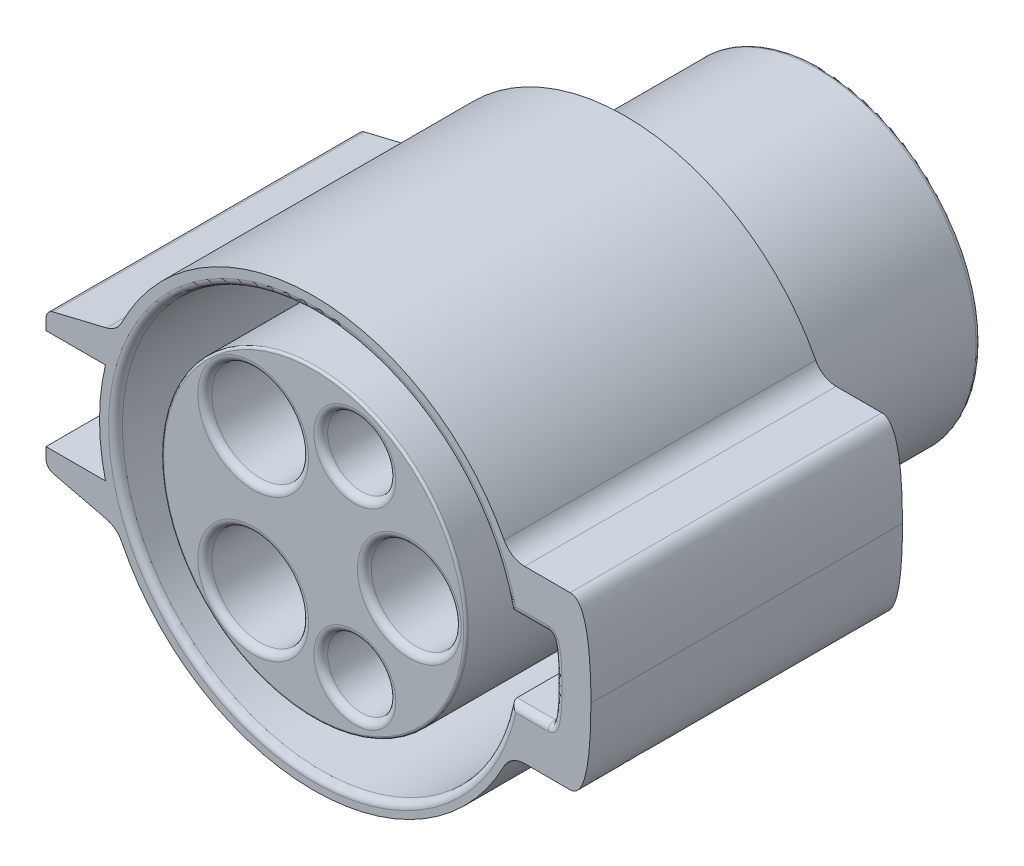
SolidWorks part; units mm, degrees
ref_plane "Front Plane" through (0, 0, 0) normal (0, 0, 1) x (1, 0, 0)
ref_plane "Top Plane" through (0, 0, 0) normal (0, 1, 0) x (1, 0, 0)
ref_plane "Right Plane" through (0, 0, 0) normal (1, 0, 0) x (0, 0, -1)
sketch "Sketch1" plane through (0, 0, 0) normal (0, 0, 1) x (-1, 0, 0)
  line L0 (21.5636, -9.4046) -> (28.6554, -7.6949)
  line L1 (29.4084, -6.7135) -> (29.4084, -5.5277)
  line L2 (29.4084, -5.5277) -> (22.8364, -5.5277)
  line L3 (22.8364, 5.5213) -> (29.4084, 5.5213)
  line L4 (-28.2678, -9.3983) -> (-21.6527, -9.3983)
  line L5 (-21.6499, 9.3983) -> (-28.2678, 9.3983)
  line L6 (29.4084, 5.5213) -> (29.4084, 6.702)
  line L7 (28.6554, 7.6834) -> (21.5636, 9.3983)
  line L14 (-25.8569, -4.2807) -> (-21.6527, -4.2807)
  line L17 (-21.6805, 4.2804) -> (-25.8569, 4.2804)
  circle A1 centre (-0.0432, -0.0032) radius 16.764
  arc A5 (-21.6805, 4.2804) -> (-21.6527, -4.2807) centre (-0.1647, 0.0697) cw
  arc A6 (28.6554, -7.6949) -> (29.4084, -6.7135) centre (28.3924, -6.7135) ccw
  arc A14 (29.4084, 6.702) -> (28.6554, 7.6834) centre (28.3924, 6.702) ccw
  arc A17 (-21.6499, 9.3983) -> (21.5636, 9.3983) centre (-0.0432, -0.0032) cw
  arc A18 (22.8636, 5.5213) -> (22.8636, -5.5277) centre (-0.0432, -0.0032) cw
  arc A19 (21.5636, -9.4046) -> (-21.6527, -9.3983) centre (-0.0432, -0.0032) cw
  spline S4 degree 3 poles (-28.2678, 9.3983) (-28.4851, 9.4005) (-28.824, 9.2766) (-29.1971, 8.9393) (-29.4861, 8.4857) (-29.7884, 7.7976) (-30.0551, 6.8265) (-30.2703, 5.5562) (-30.4123, 4.2127) (-30.5275, 2.3814) (-30.5538, 0.9563) (-30.5538, 0) knots 0.008178 0.008178 0.008178 0.008178 0.0625 0.125 0.1875 0.25 0.375 0.5 0.625 0.75 0.991406 0.991406 0.991406 0.991406 weights 1 1 1 1 1 1 1 1 1 1 1 1
  spline S5 degree 3 poles (-30.5538, 0) (-30.5538, -0.9571) (-30.5275, -2.3834) (-30.412, -4.2161) (-30.2697, -5.5604) (-30.0541, -6.8314) (-29.7867, -7.8028) (-29.4835, -8.4907) (-29.1934, -8.9439) (-28.8202, -9.2785) (-28.4823, -9.4007) (-28.2678, -9.3983) knots 0.008575 0.008575 0.008575 0.008575 0.25 0.375 0.5 0.625 0.75 0.8125 0.875 0.9375 0.991042 0.991042 0.991042 0.991042 weights 1 1 1 1 1 1 1 1 1 1 1 1
  spline S10 degree 3 poles (-25.8569, 4.2804) (-25.8911, 4.2808) (-25.9613, 4.2635) (-26.0812, 4.1882) (-26.1906, 4.0282) (-26.2866, 3.801) (-26.3835, 3.4669) (-26.4672, 3.0119) (-26.5335, 2.4318) (-26.5768, 1.8286) (-26.6112, 1.0239) (-26.619, 0.4081) (-26.6189, 0) knots 0.011727 0.011727 0.011727 0.011727 0.03125 0.0625 0.125 0.1875 0.25 0.375 0.5 0.625 0.75 0.986732 0.986732 0.986732 0.986732 weights 1 1 1 1 1 1 1 1 1 1 1 1 1
  spline S11 degree 3 poles (-26.6189, 0) (-26.619, -0.4097) (-26.6111, -1.0278) (-26.5764, -1.8353) (-26.5327, -2.4403) (-26.4657, -3.0221) (-26.381, -3.478) (-26.2827, -3.8122) (-26.1847, -4.0386) (-26.0733, -4.1975) (-25.9519, -4.266) (-25.8849, -4.2809) (-25.8569, -4.2807) knots 0.013201 0.013201 0.013201 0.013201 0.25 0.375 0.5 0.625 0.75 0.8125 0.875 0.9375 0.96875 0.984802 0.984802 0.984802 0.984802 weights 1 1 1 1 1 1 1 1 1 1 1 1 1
  point P2 (21.5636, -9.4046)
  point P5 (21.5636, 9.3983)
  point P7 (0, 0)
  point P10 (-21.5632, -9.461)
  point P11 (-21.6527, -9.3983)
extrude "Boss-Extrude2" add sketch "Sketch1" along normal blind 31.75 contours S4 S5 L4 A19 L0 A6 L1 L2 A18 L3 L6 A14 L7 A17 L5 S11 S10 L17 A5 L14 | A1 region at (0.0465, 22.804, 0) region at (0.0432, 0.0032, 0)
sketch "sockets" plane through (0, 0, 31.75) normal (0, 0, 1) x (1, 0, 0)
  circle A0 centre (10.5791, 0) radius 4.953
  circle A1 centre (4.572, -10.541) radius 3.7465
  circle A2 centre (-6.604, -7.8359) radius 5.334
  circle A3 centre (-6.604, 7.8359) radius 5.334
  circle A4 centre (4.572, 10.541) radius 3.7465
sketch "Sketch3" plane through (0, 0, 0) normal (0, 0, 1) x (1, 0, 0)
  line L8 (-29.4084, 5.5277) -> (-22.8636, 5.5277)
  line L9 (-29.4084, 6.7135) -> (-29.4084, 5.5277)
  line L10 (-21.5636, 9.4046) -> (-28.6554, 7.6949)
  line L11 (28.2678, 9.3983) -> (21.6527, 9.3983)
  line L12 (21.6499, -9.3983) -> (28.2678, -9.3983)
  line L13 (-28.6554, -7.6834) -> (-21.5636, -9.3983)
  line L14 (-29.4084, -5.5213) -> (-29.4084, -6.702)
  line L15 (-22.8636, -5.5213) -> (-29.4084, -5.5213)
  line L16 (-29.4084, 5.5277) -> (-22.8636, 5.5277)
  line L17 (-29.4084, 6.7135) -> (-29.4084, 5.5277)
  line L18 (-21.5636, 9.4046) -> (-28.6554, 7.6949)
  line L19 (28.2678, 9.3983) -> (21.6527, 9.3983)
  line L20 (21.6499, -9.3983) -> (28.2678, -9.3983)
  line L21 (-28.6554, -7.6834) -> (-21.5636, -9.3983)
  line L22 (-29.4084, -5.5213) -> (-29.4084, -6.702)
  line L23 (-22.8636, -5.5213) -> (-29.4084, -5.5213)
  circle A0 centre (0.0432, 0.0032) radius 16.5062
  arc A5 (-22.8636, 5.5277) -> (-22.8636, -5.5213) centre (0.0432, 0.0032) ccw
  arc A6 (-28.6554, 7.6949) -> (-29.4084, 6.7135) centre (-28.3924, 6.7135) ccw
  arc A7 (21.6527, 9.3983) -> (-21.5636, 9.4046) centre (0.0432, 0.0032) ccw
  arc A8 (-21.5636, -9.3983) -> (21.6499, -9.3983) centre (0.0432, 0.0032) ccw
  arc A9 (-29.4084, -6.702) -> (-28.6554, -7.6834) centre (-28.3924, -6.702) ccw
  arc A10 (-22.8636, 5.5277) -> (-22.8636, -5.5213) centre (0.0432, 0.0032) ccw
  arc A11 (-28.6554, 7.6949) -> (-29.4084, 6.7135) centre (-28.3924, 6.7135) ccw
  arc A12 (21.6527, 9.3983) -> (-21.5636, 9.4046) centre (0.0432, 0.0032) ccw
  arc A13 (-21.5636, -9.3983) -> (21.6499, -9.3983) centre (0.0432, 0.0032) ccw
  arc A14 (-29.4084, -6.702) -> (-28.6554, -7.6834) centre (-28.3924, -6.702) ccw
  spline S2 degree 3 poles (2242.6, 2023.5461) (-79.1173, -234.406) (34.2531, -56.736) (30.412, 4.2161) (30.2697, 5.5604) (30.0541, 6.8314) (29.7867, 7.8028) (29.4835, 8.4907) (29.1934, 8.9439) (24.7293, 12.9464) (-10.04, -13.6045) (-2104.1567, -2099.7835) knots -15.84419 -15.84419 -15.84419 -15.84419 0.25 0.375 0.5 0.625 0.75 0.8125 0.875 0.9375 2.948231 2.948231 2.948231 2.948231 weights 1 1 1 1 1 1 1 1 1 1 1 1 only from (30.5538, 0) to (28.2678, 9.3983)
  spline S3 degree 3 poles (-2104.6142, 2100.0497) (-10.3685, 13.8122) (24.7169, -12.9902) (29.1971, -8.9393) (29.4861, -8.4857) (29.7884, -7.7976) (30.0551, -6.8265) (30.2703, -5.5562) (30.4123, -4.2127) (34.2496, 56.75) (-79.1081, 234.4143) (2242.6167, -2023.5315) knots -1.966154 -1.966154 -1.966154 -1.966154 0.0625 0.125 0.1875 0.25 0.375 0.5 0.625 0.75 16.858679 16.858679 16.858679 16.858679 weights 1 1 1 1 1 1 1 1 1 1 1 1 only from (28.2678, -9.3983) to (30.5538, 0)
  spline S4 degree 3 poles (30.5538, 0) (30.5538, 0.9571) (30.5275, 2.3834) (30.412, 4.2161) (30.2697, 5.5604) (30.0541, 6.8314) (29.7867, 7.8028) (29.4835, 8.4907) (29.1934, 8.9439) (28.8202, 9.2785) (28.4823, 9.4007) (28.2678, 9.3983) knots 0.008575 0.008575 0.008575 0.008575 0.25 0.375 0.5 0.625 0.75 0.8125 0.875 0.9375 0.991042 0.991042 0.991042 0.991042 weights 1 1 1 1 1 1 1 1 1 1 1 1
  spline S5 degree 3 poles (28.2678, -9.3983) (28.4851, -9.4005) (28.824, -9.2766) (29.1971, -8.9393) (29.4861, -8.4857) (29.7884, -7.7976) (30.0551, -6.8265) (30.2703, -5.5562) (30.4123, -4.2127) (30.5275, -2.3814) (30.5538, -0.9563) (30.5538, 0) knots 0.008178 0.008178 0.008178 0.008178 0.0625 0.125 0.1875 0.25 0.375 0.5 0.625 0.75 0.991406 0.991406 0.991406 0.991406 weights 1 1 1 1 1 1 1 1 1 1 1 1
  dimension "D1" = 0
extrude "Boss-Extrude3" add sketch "Sketch3" against normal blind 2.54
sketch "Sketch4" plane through (0, 0, 0) normal (0, 0, 1) x (1, 0, 0)
  circle A2 centre (0.0432, 0.0032) radius 17.526
  dimension "D1" = 35.052
extrude "Boss-Extrude4" add sketch "Sketch4" against normal blind 24.13
extrude "Cut-Extrude7" cut sketch "sockets" against normal blind 25.4
sketch "Sketch9" plane through (0, 0, -24.13) normal (0, 0, 1) x (1, 0, 0)
  circle A2 centre (4.572, 10.541) radius 4.6482
  circle A3 centre (4.572, -10.541) radius 4.6482
  dimension "D1" = 9.2964
sketch "Sketch10" plane through (0, 0, -24.13) normal (0, 0, 1) x (1, 0, 0)
  circle A2 centre (-6.604, 7.8359) radius 5.6261
  circle A3 centre (-6.604, -7.8359) radius 5.6261
  dimension "D1" = 11.2522
sketch "Sketch11" plane through (0, 0, -24.13) normal (0, 0, 1) x (1, 0, 0)
  circle A1 centre (10.5791, 0) radius 5.6642
  dimension "D1" = 11.3284
sketch "pin holes" plane through (0, 0, -24.13) normal (0, 0, 1) x (1, 0, 0)
  circle A0 centre (4.572, 10.541) radius 0.762
  circle A1 centre (10.5791, 0) radius 1.397
  circle A2 centre (4.572, -10.541) radius 0.762
  circle A3 centre (-6.604, -7.8359) radius 1.8415
  circle A4 centre (-6.604, 7.8359) radius 1.8415
  dimension "D1" = 3.683
  dimension "D2" = 1.524
  dimension "D3" = 2.794
sketch "Sketch12" plane through (0, 0, 0) normal (0, 0, 1) x (1, 0, 0)
  line L0 (-22.8413, 5.5037) -> (-26.7275, 5.5245)
  line L1 (-26.7275, 5.5245) -> (-26.7275, -5.5245)
  line L2 (-26.7275, -5.5245) -> (-22.8363, -5.5245)
  arc A0 (-22.8413, 5.5037) -> (-22.8363, -5.5245) centre (0, 0) ccw
extrude "Boss-Extrude8" add sketch "Sketch12" along normal blind 28.0924
sketch "Sketch13" plane through (0, 0, 0) normal (0, 0, 1) x (1, 0, 0)
  line L0 (-22.8413, 5.5037) -> (-26.7275, 5.5245)
  line L1 (-26.7275, 5.5245) -> (-26.7275, -5.5245)
  line L2 (-26.7275, -5.5245) -> (-22.8363, -5.5245)
  arc A0 (-22.8413, 5.5037) -> (-22.8363, -5.5245) centre (0, 0) ccw
  point P5 (0, 0)
extrude "Cut-Extrude9" cut sketch "Sketch13" along normal blind 12.1158
chamfer "Chamfer4" distance 4.572 angle 45 1 edges at (-26.7275, 0.0016, 28.0924)
sketch "screwholes" plane through (0, 0, -24.13) normal (0, 0, 1) x (1, 0, 0)
  circle A0 centre (1.2752, 0.003) radius 1.27
  circle A1 centre (-15.311, 0.005) radius 1.27
extrude "Cut-Extrude14" cut sketch "screwholes" along normal blind 8.89
extrude "Cut-Extrude15" cut sketch "Sketch11" along normal blind 22.86
extrude "Cut-Extrude16" cut sketch "Sketch9" along normal blind 26.289
extrude "Cut-Extrude17" cut sketch "Sketch10" along normal blind 26.7462
extrude "Cut-Extrude18" cut sketch "pin holes" along normal blind 57.15
fillet "Fillet2" radius 2.54 4 edges at (-21.5636, 9.4046, 14.605) (-21.5636, -9.3983, 14.605) (21.6499, -9.3983, 14.605) (21.6527, 9.3983, 14.605)
fillet "Fillet1" radius 0.762 1 edges at (-26.7275, 0.0016, 12.1158)
fillet "Fillet3" radius 0.762 5 edges at (8.3185, -10.541, 31.75) (-1.27, -7.8359, 31.75) (-1.27, 7.8359, 31.75) (8.3185, 10.541, 31.75) (15.5321, 0, 31.75)
fillet "Fillet4" radius 0.762 4 edges at (-21.7591, -0.141, 31.75)
fillet "Fillet5" radius 2.54 1 edges at (17.5692, 0.0032, -2.54)
fillet "Fillet7" radius 0.254 1 edges at (16.8072, 0.0032, 31.75)
fillet "Fillet8" radius 0.508 5 edges at (-0.9779, 7.8359, -24.13) (9.2202, 10.541, -24.13) (16.2433, 0, -24.13) (9.2202, -10.541, -24.13) (-0.9779, -7.8359, -24.13)
fillet "Fillet9" radius 0.508 1 edges at (17.5692, 0.0032, -24.13)
